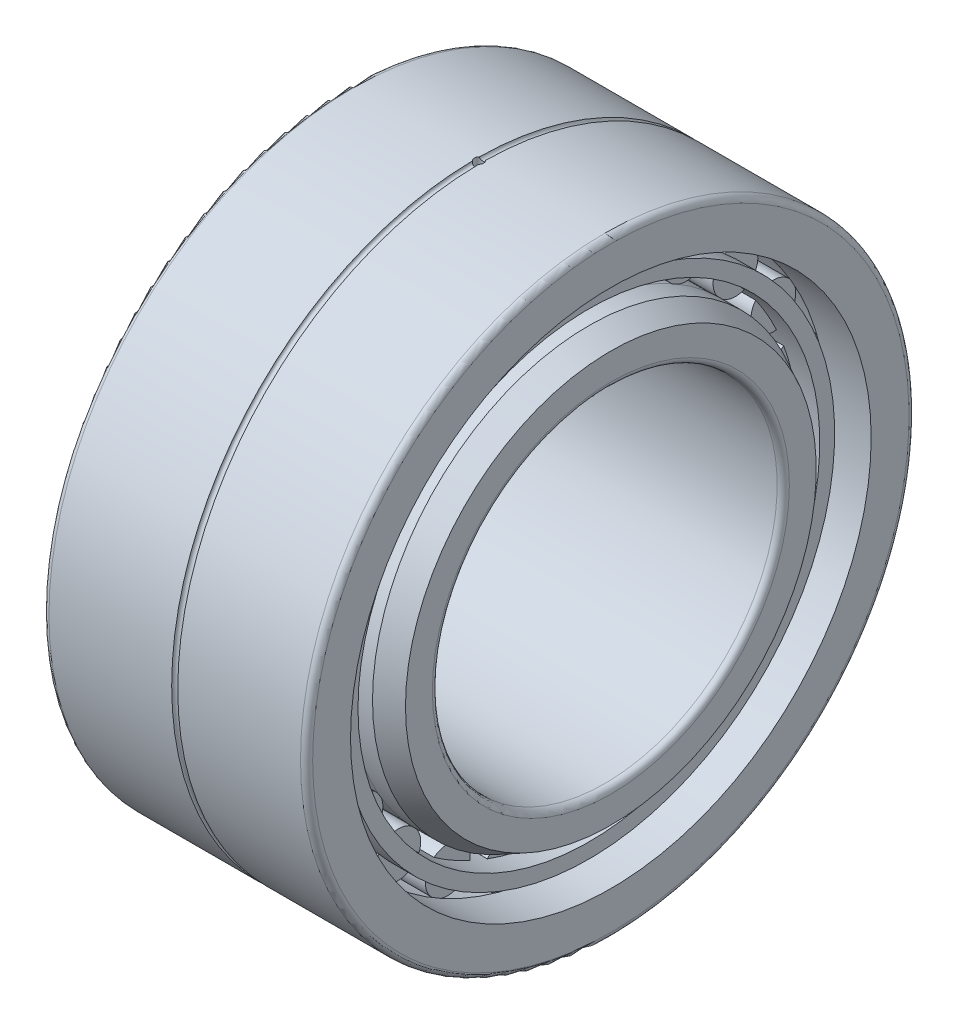
SolidWorks part; units mm, degrees
note: The reader was unsure of these and kept them because the rebuilt part matched: shared geometry of "Sketch1<4>".
ref_plane "Front" through (0, 0, 0) normal (0, 0, 1) x (1, 0, 0)
ref_plane "Top" through (0, 0, 0) normal (0, 1, 0) x (1, 0, 0)
ref_plane "Right" through (0, 0, 0) normal (1, 0, 0) x (0, 0, -1)
sketch "Sketch1" plane through (0, 0, 0) normal (0, 0, 1) x (1, 0, 0)
  line L0 (-6.5, 0) -> (27.2471, 0) construction
  line L1 (0, 12.8333) -> (0, 73.1983) construction
  line L2 (-6.2, 8.5) -> (6.2, 8.5)
  line L3 (-6.5, 8.8) -> (-6.5, 10.6667)
  line L4 (-6.5, 10.6667) -> (6.5, 10.6667)
  line L5 (6.5, 8.8) -> (6.5, 10.6667)
  line L6 (-6.5, 12.8333) -> (6.5, 12.8333)
  line L7 (-6.5, 12.8333) -> (-6.5, 14.7)
  line L8 (-6.2, 15) -> (6.2, 15)
  line L9 (6.5, 12.8333) -> (6.5, 14.7)
  line L10 (-4.3333, 10.6467) -> (4.3333, 10.6467)
  line L11 (-4.3333, 10.6467) -> (-4.3333, 12.8533)
  line L12 (-4.3333, 12.8533) -> (4.3333, 12.8533)
  line L13 (4.3333, 10.6467) -> (4.3333, 12.8533)
  line L14 (-8.6667, 11.75) -> (0, 11.75)
  line L15 (-6.5, 10.125) -> (-5.4167, 10.6667)
  line L16 (-5.4167, 11.3822) -> (5.4167, 11.3822)
  line L17 (-5.4167, 11.3822) -> (-5.4167, 12.1178)
  line L18 (-5.4167, 12.1178) -> (5.4167, 12.1178)
  line L19 (5.4167, 11.3822) -> (5.4167, 12.1178)
  line L20 (6.5, 10.125) -> (5.4167, 10.6667)
  line L21 (-4.3333, 10.6667) -> (-6.5, 10.6667)
  arc A0 (-6.5, 14.7) -> (-6.2, 15) centre (-6.2, 14.7) cw
  arc A1 (6.5, 14.7) -> (6.2, 15) centre (6.2, 14.7) ccw
  arc A2 (-6.2, 8.5) -> (-6.5, 8.8) centre (-6.2, 8.8) cw
  arc A3 (6.5, 8.8) -> (6.2, 8.5) centre (6.2, 8.8) cw
  point P17 (-6.5, 15)
  point P20 (6.5, 15)
  point P29 (-4.3333, 11.75)
  point P34 (-5.4167, 11.75)
  point P35 (0, 12.1178)
  dimension "D1" = 2.1667
  dimension "D2" = 0.5417
  dimension "D3" = 21.3333
revolve "Revolve1" add sketch "Sketch1" angle 360 about L0
sketch "Sketch7" plane through (0, 0, 0) normal (0, 0, 1) x (1, 0, 0)
  line L0 (-4.3333, 12.8333) -> (4.3333, 12.8333) construction
  line L5 (-4.2611, 13.2667) -> (4.2611, 13.2667)
  line L6 (4.3333, 13.1944) -> (4.3333, 12.6333)
  line L7 (4.3333, 12.6333) -> (-4.3333, 12.6333)
  line L8 (-4.3333, 12.6333) -> (-4.3333, 13.1944)
  line L9 (0, 0) -> (26.2189, 0) construction
  arc A0 (-4.2611, 13.2667) -> (-4.3333, 13.1944) centre (-4.3333, 13.2667) ccw
  arc A1 (4.3333, 13.1944) -> (4.2611, 13.2667) centre (4.3333, 13.2667) ccw
  dimension "D3" = 0.1444
  dimension "D1" = 0.2
  dimension "D2" = 0.4333
revolve "Cut-Revolve2" cut sketch "Sketch7" angle 360 about L9
sketch "Sketch2" plane through (0, 0, 0) normal (0, 0, 1) x (1, 0, 0)
  line L0 (-8.6667, 11.75) -> (0, 11.75) construction
  line L1 (-4.3333, 11.75) -> (4.3333, 11.75)
  line L2 (4.3333, 10.6467) -> (4.3333, 12.8533) construction
  line L3 (-4.3333, 10.6467) -> (-4.3333, 12.8533) construction
  line L4 (-4.3333, 12.8533) -> (4.3333, 12.8533) construction
  line L5 (4.3333, 11.75) -> (4.3333, 12.8533)
  line L6 (-4.3333, 11.75) -> (-4.3333, 12.8533)
  line L7 (-4.3333, 12.8533) -> (4.3333, 12.8533)
  line L8 (-21.3719, 11.75) -> (15.9265, 11.75) construction
revolve "Revolve2" add sketch "Sketch2" angle 360 about L8
revolve "Revolve3" add sketch "Sketch1<4>" angle 360 about L0
sketch "Sketch1<4>" plane through (0, 0, 0) normal (0, 0, 1) x (1, 0, 0) same geometry as "Sketch1"
pattern_circular "Circular-Pattern1" count 24 over 360 about axis through (0, 0, 0) along (1, 0, 0) of bodies 108
sketch "Sketch4" plane through (0, 0, 0) normal (0, 0, 1) x (1, 0, 0)
  line L0 (5.4167, 11.3822) -> (5.4167, 12.1178) construction
  line L1 (-5.4167, 11.3822) -> (-5.4167, 12.1178) construction
  line L2 (-5.4167, 12.1178) -> (5.4167, 12.1178) construction
  line L3 (-5.4167, 11.3822) -> (5.4167, 11.3822) construction
  line L4 (5.4167, 11.3822) -> (5.4167, 12.1178)
  line L5 (-5.4167, 11.3822) -> (-5.4167, 12.1178)
  line L6 (-5.4167, 12.1178) -> (5.4167, 12.1178)
  line L7 (-5.4167, 11.3822) -> (5.4167, 11.3822)
revolve "Revolve4" add sketch "Sketch4" angle 360 about axis through (-6.5, 0, 0) along (1, 0, 0)
sketch "Sketch5" plane through (0, 0, 0) normal (0, 1, 0) x (1, 0, 0)
  line L0 (-3.429, 0) -> (24.4782, 0) construction
  line L1 (6.2, 15) -> (-6.2, 15) construction
  circle A0 centre (0, 15) radius 0.15
  dimension "D2" = 0.3
revolve "Cut-Revolve1" cut sketch "Sketch5" angle 360 about L0
ref_plane "Plane1" through (0, 15, 0) normal (0, 1, 0) x (-1, 0, 0)
sketch "Sketch6" plane through (0, 15, 0) normal (0, 1, 0) x (1, 0, 0)
  line L16 (-6.5, 14.7) -> (-6.5, -14.7) construction
  circle A0 centre (0, 0) radius 0.225
  dimension "D1" = 0.45
  dimension "D2" = 6.5
extrude "Cut-Extrude1" cut sketch "Sketch6" against normal blind 2.1667
mirror "Mirror1" about plane through (0, 0, 0) normal (0, 1, 0) of "Cut-Extrude1"
equation "\"D1@Sketch1\" =  ( \"DD@Sketch1\" - \"XD@Sketch1\" )  / 6"
equation "\"ZJ@Sketch1\" = (  \"DD@Sketch1\" + \"XD@Sketch1\" )  / 2"
equation "\"GZZJ@Sketch1\" = \"D1@Sketch1\" + 0.04"
equation "\"GZC@Sketch1\" = \"DBC@Sketch1\" / 3 * 2"
equation "\"GJZ@Sketch1\" =  ( \"DBC@Sketch1\" + \"GZC@Sketch1\" )  / 2"
equation "\"D2@Sketch1\" = \"D1@Sketch1\" / 4"
equation "\"D2@Sketch5\" = \"XR@Sketch1\""
equation "\"GJZJ@Sketch1\" = \"GZZJ@Sketch1\" / 3"
equation "\"D1@Sketch6\" =\"D2@Sketch5\" * 1.5"
equation "\"D1@Plane1\" = \"DD@Sketch1\" / 2"
equation "\"D1@Cut-Extrude1\" = \"D1@Sketch1\""
equation "\"D2@Sketch6\" = \"DBC@Sketch1\" / 2"
equation "\"D1@Circular-Pattern1\" = int ( 3.14159265 / atn (  ( \"GZZJ@Sketch1\" / 2 )  / sqr ( \"XD@Sketch1\" * \"XD@Sketch1\" / 4 -  ( \"GZZJ@Sketch1\" / 2 )  *  ( \"GZZJ@Sketch1\" / 2 )  )  )  ) "
equation "\"D3@Sketch1\" = \"XD@Sketch1\" + 2 * \"D1@Sketch1\""
equation "\"D2@Sketch7\" = \"D1@Sketch1\" / 5"
equation "\"D3@Sketch7\" = \"D2@Sketch7\" / 3"
